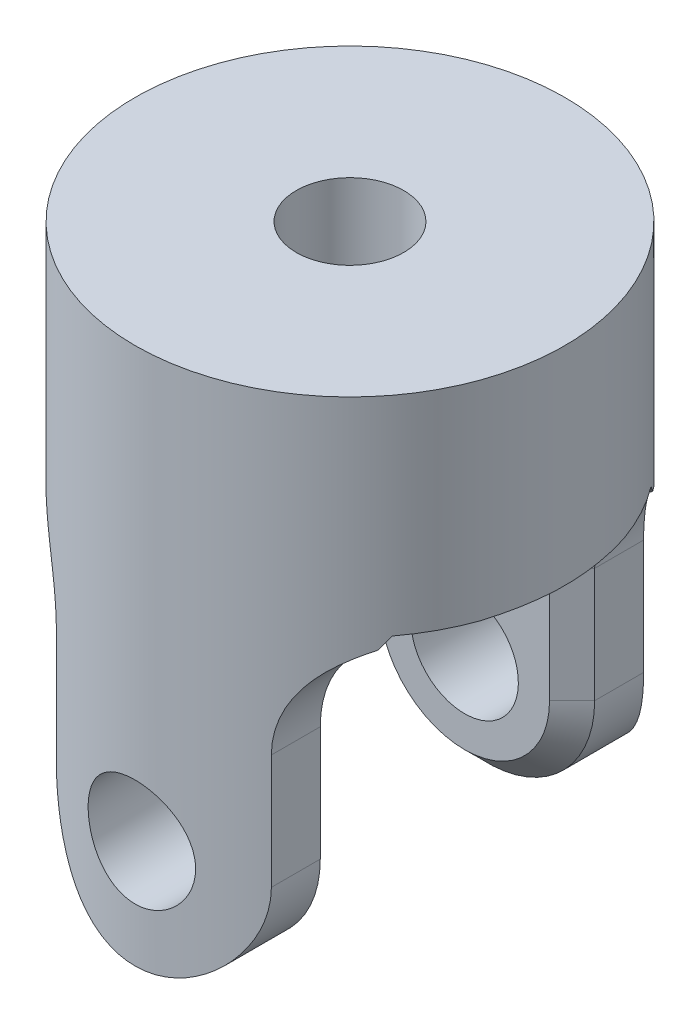
SolidWorks part; units mm, degrees
ref_plane "Front" through (0, 0, 0) normal (0, 0, 1) x (1, 0, 0)
ref_plane "Top" through (0, 0, 0) normal (0, 1, 0) x (-1, 0, 0)
ref_plane "Right" through (0, 0, 0) normal (1, 0, 0) x (0, 0, -1)
sketch "Sketch1" plane through (0, 0, 0) normal (0, 1, 0) x (-1, 0, 0)
  circle A0 centre (0, 0) radius 19.05
  dimension "D1" = 38.1
extrude "Base-Extrude" add sketch "Sketch1" along normal blind 47.625
sketch "Sketch2" plane through (0, 0, 0) normal (0, 0, 1) x (1, 0, 0)
  line L0 (0, 0) -> (0, 23.7435) construction
  line L1 (9.525, 9.525) -> (9.525, 19.685)
  line L2 (-9.525, 9.525) -> (-9.525, 19.685)
  line L3 (19.05, 29.21) -> (19.05, 0)
  line L4 (-19.05, 47.625) -> (-19.05, 0) construction
  line L5 (-19.05, 0) -> (-19.05, 29.21)
  line L6 (19.05, 0) -> (-19.05, 0) construction
  arc A0 (-9.525, 9.525) -> (9.525, 9.525) centre (0, 9.525) ccw
  arc A1 (9.525, 19.685) -> (19.05, 29.21) centre (19.05, 19.685) cw
  arc A2 (-9.525, 19.685) -> (-19.05, 29.21) centre (-19.05, 19.685) ccw
  dimension "D3" = 9.525
  dimension "D2" = 19.05
  dimension "D4" = 29.21
extrude "Cut-Extrude1" cut sketch "Sketch2" against normal through all and the other way through all flip side to cut
sketch "Sketch8" plane through (0, 0, 0) normal (1, 0, 0) x (0, 0, -1)
  line L0 (-19.05, 0) -> (19.05, 0) construction
  line L1 (-10.16, 0) -> (-10.16, 29.1452)
  line L2 (10.16, 29.1452) -> (-10.16, 29.1452)
  line L3 (10.16, 29.1452) -> (10.16, 0)
  line L4 (0, 0) -> (0, 14.3858) construction
  point P4 (0, 0)
  dimension "D1" = 29.1452
  dimension "D2" = 20.32
extrude "Cut-Extrude5" cut sketch "Sketch8" against normal through all and the other way through all flip side to cut
sketch "Sketch11" plane through (0, 0, 0) normal (0, 0, 1) x (1, 0, 0)
  circle A0 centre (0, 9.525) radius 4.7625
  dimension "D1" = 9.525
extrude "Cut-Extrude6" cut sketch "Sketch11" against normal through all and the other way through all
sketch "Sketch12" plane through (0, 47.625, 0) normal (0, 1, 0) x (-1, 0, 0)
  circle A0 centre (0, 0) radius 4.7625
  dimension "D1" = 9.525
extrude "Cut-Extrude7" cut sketch "Sketch12" against normal through all
ref_axis "Axis1" through (0, 97.625, 0) along (0, -1, 0)
chamfer "Chamfer1" distance 2 angle 45 10 edges at (11.3465, 25.287, 10.16) (9.525, 14.605, 10.16) (0, 0, 10.16) (-11.3465, 25.287, 10.16) (-9.525, 14.605, 10.16) (11.3465, 25.287, -10.16) (9.525, 14.605, -10.16) (-11.3465, 25.287, -10.16) (0, 0, -10.16) (-9.525, 14.605, -10.16)
